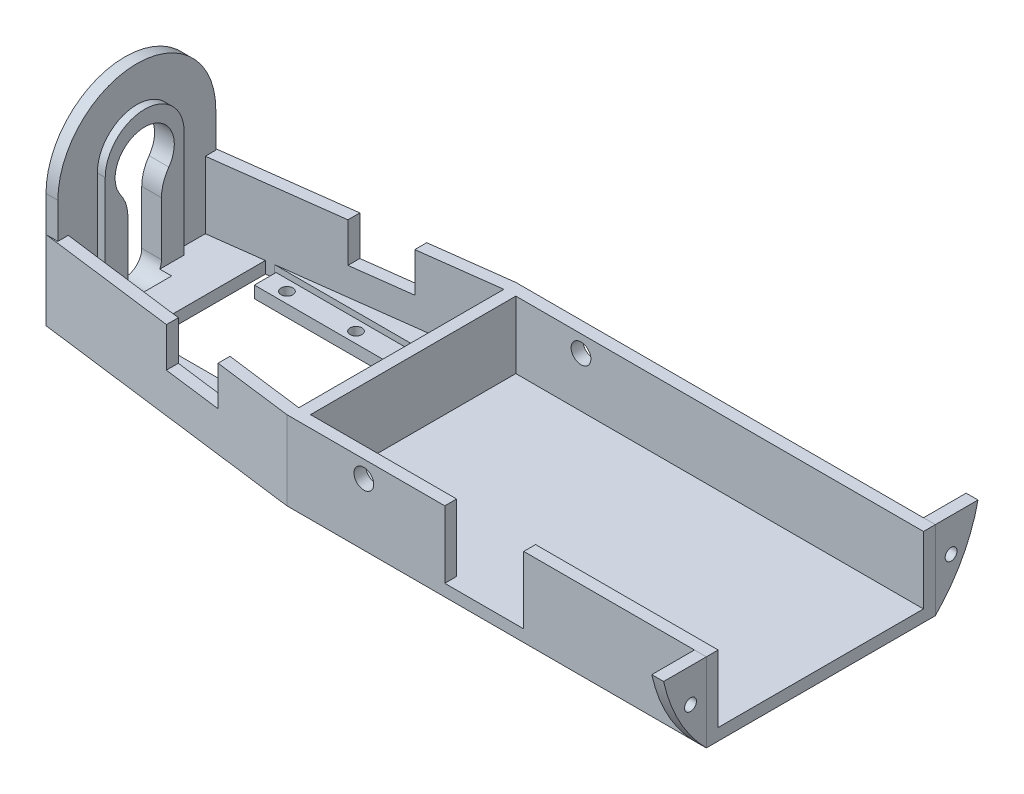
SolidWorks part; units mm, degrees
ref_plane "Front Plane" through (0, 0, 0) normal (0, 0, 1) x (1, 0, 0)
ref_plane "Top Plane" through (0, 0, 0) normal (0, 1, 0) x (1, 0, 0)
ref_plane "Right Plane" through (0, 0, 0) normal (1, 0, 0) x (0, 0, -1)
sketch "Sketch2" plane through (0, 0, 0) normal (0, 1, 0) x (1, 0, 0)
  line L0 (-119.25, 20) -> (-119.25, -20)
  line L1 (-49.25, -29) -> (57, -29)
  line L2 (-49.25, -29) -> (-49.25, 29)
  line L3 (-49.25, 29) -> (57, 29)
  line L4 (57, -29) -> (57, 29)
  line L6 (60, 12) -> (60, -39) construction
  line L7 (-119.25, -20) -> (-49.25, -29)
  line L8 (-119.25, 20) -> (-49.25, 29)
  line L9 (-46.25, -23.4) -> (-46.25, 23.4) construction
  line L10 (-46.25, 23.4) -> (-46.25, -23.4) construction
  point P0 (0, 0)
  point P8 (-49.25, 0)
  point P9 (-119.25, 0)
  point P14 (-46.25, 0)
  dimension "D1" = 3
  dimension "D2" = 58
  dimension "D3" = 40
  dimension "D4" = 70
  dimension "D5" = 3
extrude "Boss-Extrude1" add sketch "Sketch2" along normal blind 3 contours L8 L0 L7 L2 | L1 L4 L3 L2 region at (-82.1071, 0, 0) region at (3.875, 0, 0)
sketch "Sketch3" plane through (0, 0, 0) normal (0, -1, 0) x (1, 0, 0)
  line L0 (-49.25, -29) -> (57, -29) construction
  line L1 (-49.25, 29) -> (-46.25, 29)
  line L2 (-49.25, 29) -> (-49.25, -29)
  line L3 (-49.25, -29) -> (-46.25, -29)
  line L4 (-46.25, 29) -> (-46.25, -29)
  line L5 (57, 29) -> (57, -29) construction
  line L6 (-46.25, 29) -> (57, 29)
  line L7 (-46.25, 29) -> (-46.25, 26)
  line L8 (-46.25, 26) -> (57, 26)
  line L9 (57, 29) -> (57, 26)
  line L10 (-119.25, 20) -> (-49.25, 29) construction
  line L11 (57, -29) -> (-46.25, -29)
  line L12 (57, -29) -> (57, -26)
  line L13 (57, -26) -> (-46.25, -26)
  line L14 (-46.25, -29) -> (-46.25, -26)
  line L15 (-119.25, -16.9753) -> (-49.25, -25.9753)
  line L16 (-119.25, -20) -> (-49.25, -29) construction
  line L17 (-119.25, -20) -> (-119.25, 20) construction
  line L18 (-119.25, 16.9753) -> (-119.25, 20)
  line L19 (-119.25, 20) -> (-49.25, 29)
  line L20 (-49.25, 29) -> (-49.25, 25.9753)
  line L21 (-119.25, -16.9753) -> (-119.25, -20)
  line L22 (-119.25, -20) -> (-49.25, -29)
  line L23 (-49.25, -25.9753) -> (-49.25, -29)
  line L29 (-119.25, 16.9753) -> (-49.25, 25.9753)
  line M3 (-49.25, -29) -> (57, -29)
  line M4 (57, -29) -> (57, 29)
  line M5 (57, 29) -> (-49.25, 29)
  dimension "D1" = 3
  dimension "D2" = 3
  dimension "D3" = 3
  dimension "D4" = 3
  dimension "D5" = 3
extrude "Boss-Extrude2" add sketch "Sketch3" against normal blind 20 contours L4 L8 M4 M5 | L4 L2 M5 M3 | L13 L4 M4 M3 region at (-47.75, 0, 0) region at (5.375, 0, 27.5) region at (5.375, 0, -27.5)
sketch "Sketch4" plane through (0, 0, 0) normal (0, -1, 0) x (1, 0, 0)
  line L0 (-119.25, -20) -> (-119.25, 20)
  line L1 (-119.25, -20) -> (-116.25, -20)
  line L2 (-119.25, 20) -> (-116.25, 20)
  line L3 (-116.25, -20) -> (-116.25, 20)
  dimension "D1" = 3
extrude "Boss-Extrude3" add sketch "Sketch4" against normal blind 29
sketch "Sketch5" plane through (0, 3, 0) normal (0, 1, 0) x (1, 0, 0)
  line L0 (-49.25, 25.9753) -> (-116.25, 17.361)
  line L1 (-49.25, 29) -> (-49.25, -29) construction
  line L2 (-116.25, -20) -> (-116.25, 20) construction
  line L3 (-116.25, 17.361) -> (-119.25, 20)
  line L4 (-119.25, 20) -> (-49.25, 29)
  line L5 (-49.25, 29) -> (-49.25, 25.9753)
  line L6 (-49.25, -25.9753) -> (-116.25, -17.361)
  line L7 (-116.25, -17.361) -> (-119.25, -20)
  line L8 (-119.25, -20) -> (-49.25, -29)
  line L9 (-49.25, -29) -> (-49.25, -25.9753)
  dimension "D1" = 3
  dimension "D2" = 3
extrude "Boss-Extrude4" add sketch "Sketch5" along normal up to surface (17 mm away) up to face at (4.625, 20, 0)
sketch "Sketch6" plane through (-119.25, 0, 0) normal (-1, 0, 0) x (0, 0, 1)
  line L0 (20, 29) -> (-20, 29) construction
  circle A0 centre (0, 29) radius 20
extrude "Boss-Extrude5" add sketch "Sketch6" against normal up to surface (3 mm away) up to face at (-116.25, 18, 0)
sketch "Sketch7" plane through (-119.25, 0, 0) normal (-1, 0, 0) x (0, 0, 1)
  circle A0 centre (0, 29) radius 3.1
  point P21 (0, 30)
  dimension "D1" = 6.2
sketch "Sketch19" plane through (-116.25, 0, 0) normal (1, 0, 0) x (0, 0, -1)
  line L0 (20, 0) -> (-20, 0) construction
  line L1 (-10, 30) -> (-10, 0)
  line L2 (10, 30) -> (10, 0)
  line L3 (-10, 0) -> (10, 0)
  arc A0 (10, 30) -> (-10, 30) centre (0, 30) ccw
  circle A1 centre (0, 30) radius 1.5
  point P11 (0, 0)
  dimension "D1" = 20
  dimension "D2" = 3
extrude "Boss-Extrude9" add sketch "Sketch19" along normal blind 2
sketch "Sketch10" plane through (0, 0, 29) normal (0, 0, 1) x (1, 0, 0)
  circle A0 centre (-29.74, 15.6975) radius 2.5
  circle A1 centre (-29.74, 15.6975) radius 1.7272 construction
  dimension "D1" = 5
extrude "Cut-Extrude3" cut sketch "Sketch10" against normal through all both and the other way through all
sketch "Sketch16" plane through (57, 0, 0) normal (1, 0, 0) x (0, 0, -1)
  line L0 (-29, 20) -> (-39.8121, 20)
  line L1 (-29, 0) -> (-29, 20)
  line L2 (29, 20) -> (39.8121, 20)
  line L3 (29, 0) -> (29, 20)
  arc A0 (-39.8121, 20) -> (-29, 0) centre (0, 28.6) ccw
  circle A1 centre (-33, 11.5) radius 1.5 construction
  arc A2 (29, 0) -> (39.8121, 20) centre (0, 28.6) ccw
  circle A3 centre (-33, 11.5) radius 1.5
  arc A4 (-58.5297, 41.8011) -> (58.5297, 41.8011) centre (0, 28.6) ccw construction
  circle A5 centre (33, 11.5) radius 1.5
  circle A7 centre (33, 11.5) radius 1.5 construction
extrude "Boss-Extrude8" add sketch "Sketch16" against normal blind 3 separate body
sketch "Sketch18" plane through (0, 0, 29) normal (0, 0, 1) x (1, 0, 0)
  line L0 (57, 20) -> (-49.25, 20) construction
  line L1 (10.75, 20) -> (-9.25, 20)
  line L2 (10.75, 20) -> (10.75, 3)
  line L3 (10.75, 3) -> (-9.25, 3)
  line L4 (-9.25, 20) -> (-9.25, 3)
  line L5 (10.75, 5.4) -> (10.75, 17.4) construction
  line L6 (-49.25, 0) -> (57, 0) construction
  dimension "D1" = 20
  dimension "D2" = 3
extrude "Cut-Extrude5" cut sketch "Sketch18" against normal up to next (3 mm away)
sketch "Sketch20" plane through (-119.25, 0, 0) normal (-1, 0, 0) x (0, 0, 1)
  line L0 (0, 28.6) -> (0, 4.85)
  line L1 (-4.25, 28.6) -> (-4.25, 4.85)
  line L2 (4.25, 28.6) -> (4.25, 4.85)
  circle A0 centre (0, 28.6) radius 7.5
  arc A1 (-4.25, 28.6) -> (4.25, 28.6) centre (0, 28.6) cw
  arc A2 (-4.25, 4.85) -> (4.25, 4.85) centre (0, 4.85) ccw
  arc A4 (29, 0) -> (39.8121, 20) centre (0, 28.6) ccw construction
  dimension "D1" = 15
  dimension "D4" = 23.75
  dimension "D2" = 4.25
  dimension "D3" = 4.25
extrude "Cut-Extrude6" cut sketch "Sketch20" against normal blind 8 contours L1 A1 L2 A0 | A1 L1 A0 L2 | L1 A2 L2 A0 region at (-119.25, 32.705, 0) region at (-119.25, 25.5102, -4.453) region at (-119.25, 21.2141, -2.2947)
fillet "Fillet1" radius 10 2 edges at (-116.75, 22.4204, 4.25) (-116.75, 22.4204, -4.25)
sketch "Sketch21" plane through (0, 0, 0) normal (0, -1, 0) x (-1, 0, 0)
  line L1 (100.7812, -12.6909) -> (55.2812, -12.6909)
  line L2 (100.7812, -12.6909) -> (100.7812, 12.3091)
  line L3 (100.7812, 12.3091) -> (55.2812, 12.3091)
  line L4 (55.2812, -12.6909) -> (55.2812, 12.3091)
  circle A0 centre (93.2812, -15.4409) radius 1.5
  circle A1 centre (75.7812, -15.4409) radius 1.5
  circle A2 centre (58.7812, -15.4409) radius 1.5
  circle A3 centre (52.5312, -7.6909) radius 1.5
  circle A4 centre (52.5312, 7.3091) radius 1.5
  circle A5 centre (58.7812, 15.0591) radius 1.5
  circle A6 centre (75.7812, 15.0591) radius 1.5
  circle A7 centre (93.2812, 15.0591) radius 1.5
  circle A8 centre (93.2812, 15.0591) radius 1.5 construction
  circle A9 centre (75.7812, 15.0591) radius 1.5 construction
  circle A10 centre (58.7812, 15.0591) radius 1.5 construction
  circle A11 centre (52.5312, 7.3091) radius 1.5 construction
  circle A12 centre (52.5312, -7.6909) radius 1.5 construction
  circle A13 centre (58.7812, -15.4409) radius 1.5 construction
  circle A14 centre (75.7812, -15.4409) radius 1.5 construction
  circle A15 centre (93.2812, -15.4409) radius 1.5 construction
extrude "Cut-Extrude7" cut sketch "Sketch21" against normal up to next (3 mm away)
ref_plane "Plane1" through (-100.7812, 3, -12.3091) normal (0, 0, -1) x (-1, 0, 0)
sketch "Sketch23" plane through (0, 3, 0) normal (0, 1, 0) x (1, 0, 0)
  line L0 (-100.7812, -0.1909) -> (-55.2812, -0.1909) construction
  line L1 (-100.7812, -12.6909) -> (-100.7812, 12.3091) construction
  line L2 (-55.2812, 12.3091) -> (-55.2812, -12.6909) construction
  line L3 (-49.25, 25.9753) -> (-49.25, -25.9753) construction
  line L4 (-100.7812, 12.3091) -> (-98.7812, 12.3091)
  line L5 (-100.7812, 12.3091) -> (-100.7812, 17.8091)
  line L6 (-100.7812, 17.8091) -> (-98.7812, 17.8091)
  line L7 (-98.7812, 12.3091) -> (-98.7812, 17.8091)
  line L8 (-100.7812, 17.8091) -> (-49.25, 17.8091)
  line L9 (-100.7812, 17.8091) -> (-100.7812, 19.3499)
  line L10 (-100.7812, 19.3499) -> (-49.25, 19.3499)
  line L11 (-49.25, 17.8091) -> (-49.25, 19.3499)
  line L12 (-116.25, 17.361) -> (-49.25, 25.9753) construction
  line L13 (-100.7812, -12.6909) -> (-98.7812, -12.6909)
  line L14 (-100.7812, -18.1909) -> (-100.7812, -19.7317)
  line L15 (-100.7812, -12.6909) -> (-100.7812, -18.1909)
  line L16 (-98.7812, -12.6909) -> (-98.7812, -18.1909)
  line L17 (-100.7812, -18.1909) -> (-49.25, -18.1909)
  line L18 (-100.7812, -19.7317) -> (-49.25, -19.7317)
  line L19 (-49.25, -18.1909) -> (-49.25, -19.7317)
  line M19 (-100.7812, 12.3091) -> (-55.2812, 12.3091)
  line M21 (-55.2812, -12.6909) -> (-100.7812, -12.6909)
  line M29 (-49.25, -25.9753) -> (-49.25, 25.9753)
  dimension "D1" = 5.5
  dimension "D2" = 2
extrude "Cut-Extrude8" cut sketch "Sketch23" against normal up to next (3 mm away) contours L7 L6 L5 M19 | L10 L9 L6 L8 M29 | L15 L17 L16 M21 | L17 L19 L18 L14 region at (-99.7812, 3, -15.0591) region at (-75.0156, 3, -18.5795) region at (-99.7812, 3, 15.4409)
sketch "Sketch24" plane through (0, 3, 0) normal (0, 1, 0) x (1, 0, 0)
  line L0 (-100.7812, 19.3499) -> (-100.7812, -19.3499)
  line L1 (-100.7812, -19.3499) -> (-102.7812, -19.0927)
  line L2 (-100.7812, -19.3499) -> (-116.25, -17.361) construction
  line L3 (-102.7812, -19.0927) -> (-102.7812, 19.0927)
  line L4 (-116.25, 17.361) -> (-100.7812, 19.3499) construction
  line L5 (-102.7812, 19.0927) -> (-100.7812, 19.3499)
  dimension "D1" = 2
extrude "Cut-Extrude9" cut sketch "Sketch24" against normal up to next (3 mm away)
sketch "Sketch25" plane through (0, 0, 29) normal (0, 0, 1) x (1, 0, 0)
  line L0 (-119.25, 0) -> (-49.25, 0) construction
  line L1 (-69.25, 20) -> (-84.25, 20)
  line L2 (-69.25, 20) -> (-69.25, 10)
  line L3 (-69.25, 10) -> (-84.25, 10)
  line L4 (-84.25, 20) -> (-84.25, 10)
  line L5 (-49.25, 20) -> (-119.25, 20) construction
  line L6 (-49.25, 20) -> (-49.25, 0) construction
  point P7 (0, 0)
  dimension "D1" = 15
  dimension "D2" = 10
  dimension "D3" = 20
extrude "Cut-Extrude10" cut sketch "Sketch25" against normal through all
